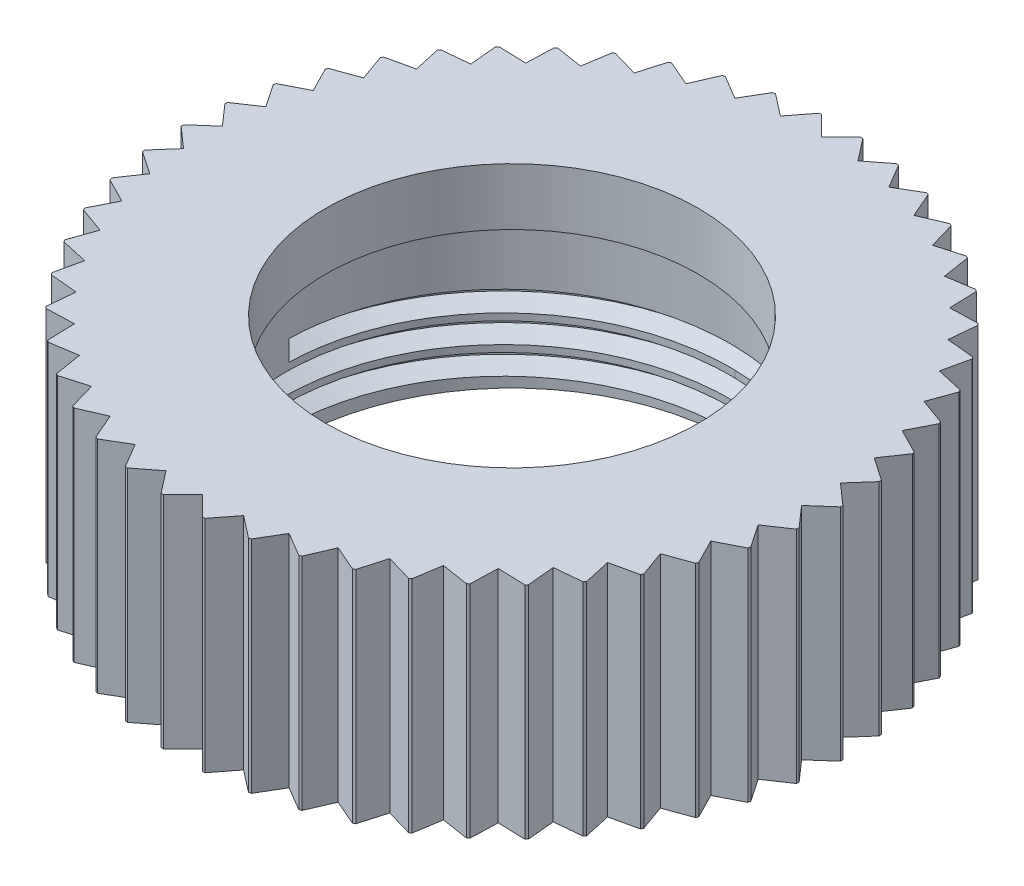
SolidWorks part; units mm, degrees
ref_plane "Front Plane" through (0, 0, 0) normal (0, 0, 1) x (1, 0, 0)
ref_plane "Top Plane" through (0, 0, 0) normal (0, 1, 0) x (1, 0, 0)
ref_plane "Right Plane" through (0, 0, 0) normal (1, 0, 0) x (0, 0, -1)
sketch "Sketch1" plane through (0, 0, 0) normal (0, 1, 0) x (1, 0, 0)
  circle A0 centre (0, 0) radius 6.015
  dimension "D1" = 12.03
extrude "Boss-Extrude1" add sketch "Sketch1" along normal blind 4.02
sketch "Sketch2" plane through (0, 4.02, 0) normal (0, 1, 0) x (1, 0, 0)
  circle A0 centre (0, 0) radius 3.4
  dimension "D1" = 6.8
extrude "Cut-Extrude1" cut sketch "Sketch2" against normal through all
sketch "Sketch3" plane through (0, 0, 0) normal (0, -1, 0) x (1, 0, 0)
  circle A0 centre (0, 0) radius 4.07
  dimension "D1" = 8.14
extrude "Cut-Extrude2" cut sketch "Sketch3" against normal blind 2.98
thread "Thread1" pitch 0.5 method cut profile "Thread Profile1" start angle 0, offset 0, length 1.25, pitch 0.5, diameter 8.14
ref_plane "Plane1" through (4.07, 0, 0) normal (0, 0, 1) x (1, 0, 0)
sketch "Thread Profile1" plane through (4.07, 0, 0) normal (0, 0, 1) x (1, 0, 0)
  line L0 (0, 0) -> (0, 0.5) construction
  line L1 (0, 0) -> (0.2706, 0.1562)
  line L2 (0.2706, 0.1562) -> (0.2706, 0.2187)
  line L3 (0.2706, 0.2187) -> (0, 0.375)
  line L4 (0.2706, 0.1875) -> (0, 0.1875) construction
  line L11 (0, 0) -> (0, 0.375)
  point P2 (0, 0)
  dimension "Pitch" = 0.5
  dimension "Profile_Angle" = 60
  dimension "Profile_Land" = 0.0625
  dimension "Profile_Height" = 0.2706
sketch "Sketch6" plane through (0, 4.02, 0) normal (0, 1, 0) x (1, 0, 0)
  line L0 (0, 5.65) -> (0.45, 6.1)
  line L1 (0.45, 6.1) -> (-0.45, 6.1)
  line L2 (-0.45, 6.1) -> (0, 5.65)
  line L3 (0, 0) -> (-0.4338, 0)
  point P5 (0, 6.1)
  dimension "D1" = 5.65
  dimension "D2" = 45
  dimension "D3" = 45
  dimension "D4" = 0
  dimension "D5" = 6.1
  dimension "D6" = 6.1
extrude "Cut-Extrude4" cut sketch "Sketch6" against normal through all contours L2 L0 L1
ref_axis "Axis1" through (0, -0.2231, 0) along (0, 1, 0)
pattern_circular "CirPattern1" count 50 over 360 about axis through (0, -0.2231, 0) along (0, 1, 0) of "Cut-Extrude4"
